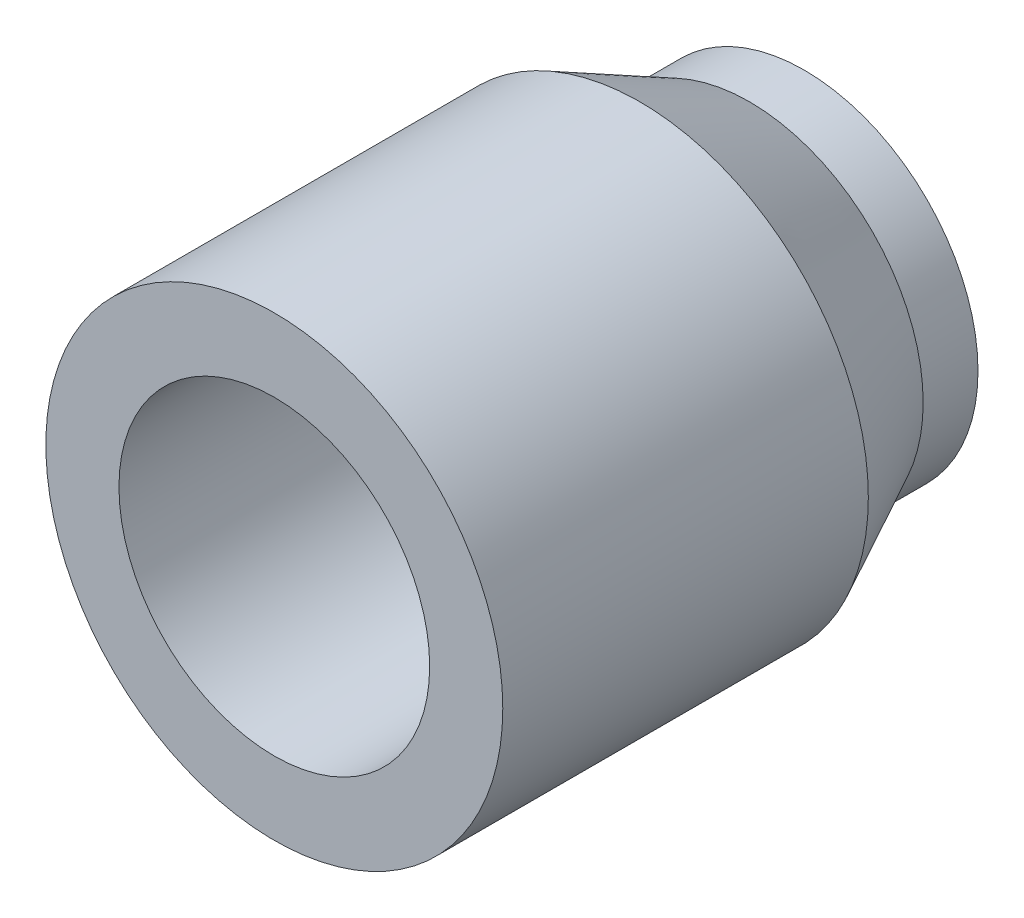
SolidWorks part; units mm, degrees
ref_plane "Front Plane" through (0, 0, 0) normal (0, 0, 1) x (1, 0, 0)
ref_plane "Top Plane" through (0, 0, 0) normal (0, 1, 0) x (1, 0, 0)
ref_plane "Right Plane" through (0, 0, 0) normal (1, 0, 0) x (0, 0, -1)
ref_plane "Plane1" through (0, 0, 3) normal (0, 0, 1) x (1, 0, 0)
sketch "Sketch1" plane through (0, 0, 0) normal (0, 0, 1) x (1, 0, 0)
  circle A0 centre (0, 0) radius 2.75
  circle A1 centre (0, 0) radius 4.75
  dimension "D1" = 5.5
  dimension "D2" = 2
sketch "Sketch2" plane through (0, 0, 3) normal (0, 0, 1) x (1, 0, 0)
  circle A0 centre (0, 0) radius 4.25
  circle A1 centre (0, 0) radius 6.25
  point P0 (0, 0)
  dimension "D1" = 8.5
  dimension "D2" = 2
loft "Loft2" add section "Sketch1" section "Sketch2" connector at (0.3205, -4.7392, 0) connector at (0.3822, -6.2383, 3)
loft "Cut-Loft1" cut section "Sketch1<68>" section "Sketch2<53>" connector at (2.6927, -0.5583, 0) connector at (4.1767, -0.7859, 3)
sketch "Sketch1<68>" plane through (0, 0, 0) normal (0, 0, 1) x (1, 0, 0) same geometry as "Sketch1"
sketch "Sketch2<53>" plane through (0, 0, 3) normal (0, 0, 1) x (1, 0, 0) same geometry as "Sketch2"
extrude "Boss-Extrude1" add sketch "Sketch1<69>" against normal blind 1.5
sketch "Sketch1<69>" plane through (0, 0, 0) normal (0, 0, 1) x (1, 0, 0) same geometry as "Sketch1"
extrude "Boss-Extrude2" add sketch "Sketch2<54>" along normal blind 10
sketch "Sketch2<54>" plane through (0, 0, 3) normal (0, 0, 1) x (1, 0, 0) same geometry as "Sketch2"
